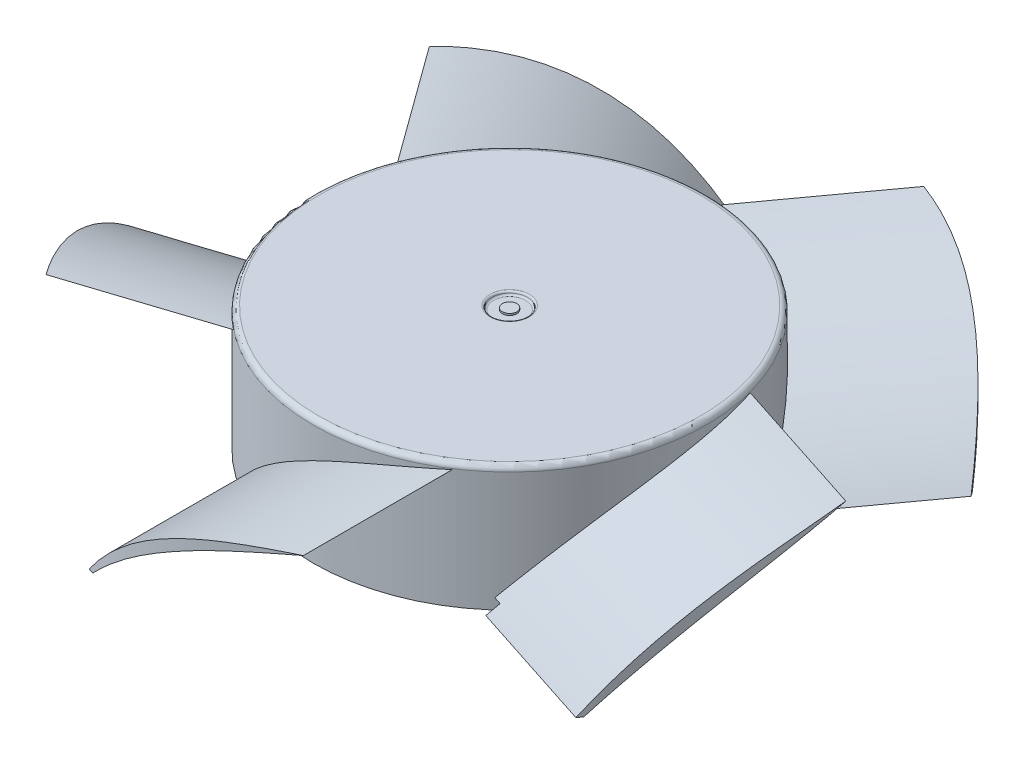
SolidWorks part; units mm, degrees
material "PE High Density"
ref_plane "Front Plane" through (0, 0, 0) normal (0, 0, 1) x (1, 0, 0)
ref_plane "Top Plane" through (0, 0, 0) normal (0, 1, 0) x (1, 0, 0)
ref_plane "Right Plane" through (0, 0, 0) normal (1, 0, 0) x (0, 0, -1)
sketch "Sketch1" plane through (0, 0, 0) normal (0, 1, 0) x (1, 0, 0)
  circle A0 centre (0, 0) radius 11
  dimension "D1" = 22
extrude "Boss-Extrude1" add sketch "Sketch1" along normal blind 7
sketch "Sketch2" plane through (0, 0, 0) normal (0, 0, 1) x (1, 0, 0)
  line L1 (-11, 0) -> (11, 0) construction
  line L2 (-6, 0) -> (-5.7, 0)
  line L3 (11, 7) -> (-11, 7) construction
  spline S0 degree 2 poles (6, 6.65) (-1.3574, 5.9183) (-6, 0) knots 0 0 0 1 1 1
  spline S1 degree 2 poles (6, 6.65) (-0.8663, 4.9932) (-5.7, 0) knots 0 0 0 1 1 1
  dimension "D1" = 5
  dimension "D2" = 0.35
  dimension "D3" = 0.3
  dimension "D4" = 5
sketch "Sketch3" plane through (0, 7, 0) normal (0, 1, 0) x (1, 0, 0)
  circle A0 centre (0, 0) radius 19.15
  dimension "D1" = 38.3
surface "Surface-Extrude1" sketch "Sketch3" parameters "D1"=7
extrude "Boss-Extrude2" add sketch "Sketch2" along normal offset from surface (17.5528 mm away) 0.6
ref_axis "Axis1" through (0, 7, 0) along (0, -1, 0)
pattern_circular "CirPattern1" count 5 over 360 about axis through (0, 7, 0) along (0, -1, 0) of "Boss-Extrude2"
sketch "Sketch4" plane through (0, 0, 0) normal (0, -1, 0) x (1, 0, 0)
  circle A0 centre (0, 0) radius 0.75
  circle A1 centre (0, 0) radius 10
  circle A2 centre (0, 0) radius 1.75
  dimension "D1" = 1.5
  dimension "D2" = 20
  dimension "D3" = 1
extrude "Cut-Extrude1" cut sketch "Sketch4" against normal offset from surface (5.5 mm away) 1.5 contours A1 A2 | A0 up to face at (0, 7, 11)
fillet "Fillet1" radius 0.3 1 edges at (0, 7, 11)
sketch "Sketch5" plane through (0, 7, 0) normal (0, 1, 0) x (1, 0, 0)
  circle A0 centre (0, 0) radius 1
  dimension "D1" = 2
extrude "Cut-Extrude2" cut sketch "Sketch5" against normal blind 0.2
fillet "Fillet2" radius 0.1 2 edges at (0, 6.8, 1) (0, 7, 1)
sketch "Sketch6" plane through (0, 0, 0) normal (0, -1, 0) x (1, 0, 0)
  circle A0 centre (0, 0) radius 11
  circle A1 centre (0, 0) radius 11.4
  dimension "D1" = 22
  dimension "D2" = 22.8
extrude "Cut-Extrude3" cut sketch "Sketch6" against normal blind 0.6
sketch "Sketch7" plane through (0, 6.8, 0) normal (0, 1, 0) x (1, 0, 0)
  circle A0 centre (0, 0) radius 0.4
  dimension "D1" = 0.8
extrude "Boss-Extrude3" add sketch "Sketch7" along normal blind 0.1
